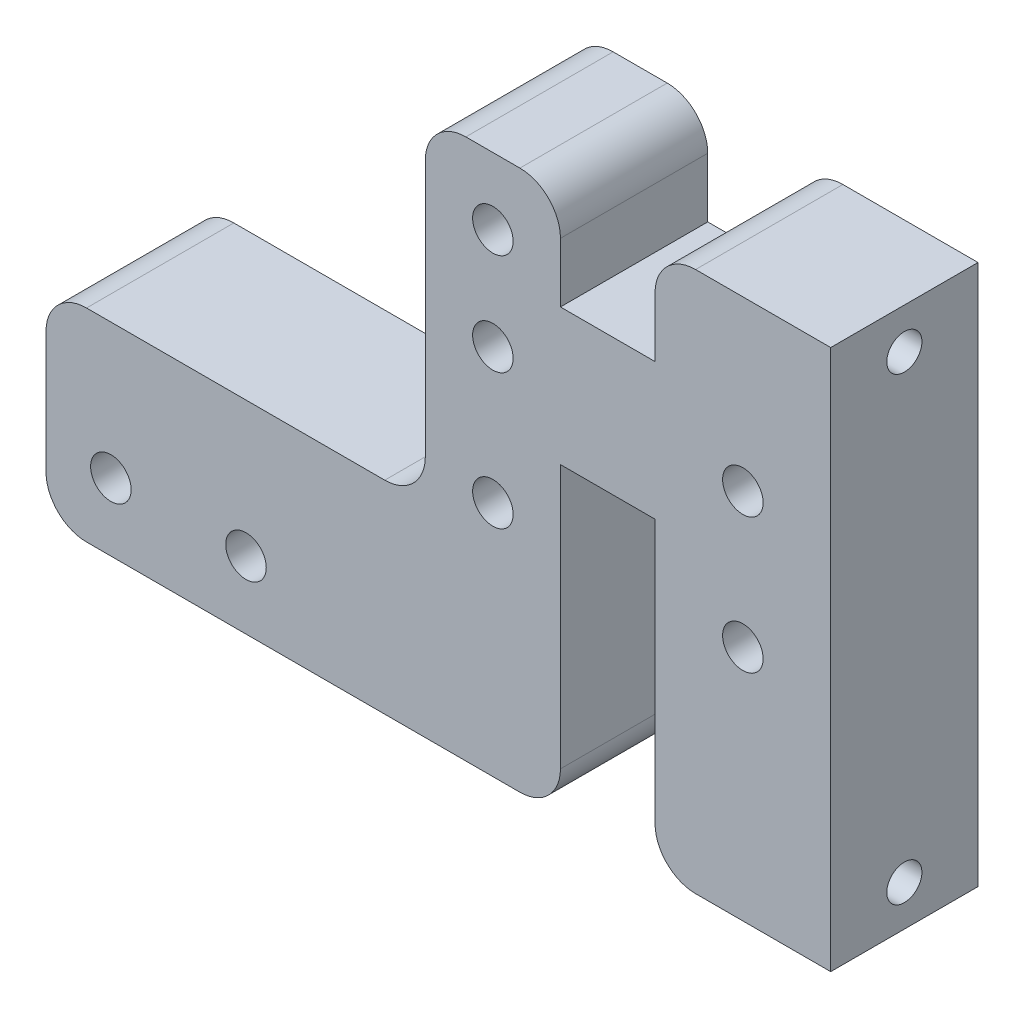
SolidWorks part; units mm, degrees
material "ナイロン"
ref_plane "正面" through (0, 0, 0) normal (0, 0, 1) x (1, 0, 0)
ref_plane "平面" through (0, 0, 0) normal (0, 1, 0) x (1, 0, 0)
ref_plane "右側面" through (0, 0, 0) normal (1, 0, 0) x (0, 0, -1)
sketch "ｽｹｯﾁ1" plane through (0, 0, 0) normal (0, 0, 1) x (1, 0, 0)
  line L0 (9.035, 20) -> (9.035, 12.6)
  line L1 (-29.035, -20) -> (29.035, -20)
  line L2 (-29.035, -20) -> (-29.035, 20)
  line L3 (-29.035, 20) -> (29.035, 20)
  line L4 (29.035, -20) -> (29.035, 20)
  line L5 (-29.035, -20) -> (29.035, 20) construction
  line L6 (-29.035, 20) -> (29.035, -20) construction
  line L7 (9.035, 12.6) -> (16.035, 12.6)
  line L8 (16.035, 12.6) -> (16.035, 20)
  line L9 (9.035, -20) -> (9.035, 2.5)
  line L10 (9.035, 2.5) -> (16.035, 2.5)
  line L11 (16.035, 2.5) -> (16.035, -20)
  line L12 (22.535, 20) -> (22.535, -20) construction
  line L13 (12.535, 12.6) -> (12.535, 2.5) construction
  line L14 (12.535, 7.55) -> (29.035, 7.55) construction
  line L15 (22.535, -2.45) -> (4.035, -2.45) construction
  line L16 (4.035, -2.45) -> (4.035, 7.55) construction
  line L17 (4.035, 7.55) -> (4.035, 15.05) construction
  circle A0 centre (22.535, 7.55) radius 1.5
  circle A1 centre (22.535, -2.45) radius 1.5
  circle A2 centre (4.035, -2.45) radius 1.5
  circle A3 centre (4.035, 7.55) radius 1.5
  circle A4 centre (4.035, 15.05) radius 1.5
  point P0 (0, 0)
  dimension "D7" = 10
  dimension "D8" = 3
  dimension "D9" = 3
  dimension "D10" = 10
  dimension "D11" = 5
  dimension "D1" = 40
  dimension "D2" = 13
  dimension "D3" = 7
  dimension "D4" = 7.4
  dimension "D5" = 58.07
  dimension "D6" = 22.5
  dimension "D12" = 7.5
extrude "ﾎﾞｽ - 押し出し1" add sketch "ｽｹｯﾁ1" along normal blind 10.9 contours L8 L7 L0 L3 L2 L1 L4 region at (-1.4569, 0.171, 0)
sketch "ｽｹｯﾁ2" plane through (29.035, 0, 0) normal (1, 0, 0) x (0, 0, -1)
  line L0 (-5.45, 20) -> (-5.45, -20) construction
  line L1 (-10.9, 20) -> (0, 20) construction
  line L2 (-10.9, -20) -> (0, -20) construction
  line L3 (0, 0) -> (-10.9, 0) construction
  line L4 (-10.9, -20) -> (-10.9, 20) construction
  circle A0 centre (-5.45, 17) radius 1.3
  circle A1 centre (-5.45, -17) radius 1.3
  dimension "D1" = 34
  dimension "D2" = 2.6
extrude "ｶｯﾄ - 押し出し1" cut sketch "ｽｹｯﾁ2" against normal up to surface (13 mm away) up to face at (16.035, 16.3, 5.45)
sketch "ｽｹｯﾁ5" plane through (0, 0, 10.9) normal (0, 0, 1) x (1, 0, 0)
  line L0 (29.035, -20) -> (29.035, 20) construction
  line L1 (-29.035, 20) -> (9.035, 20) construction
  line L2 (-8.935, 24) -> (-29.035, 24) construction
  circle A0 centre (-29.035, 24) radius 5.1
  circle A1 centre (-8.935, 24) radius 5.1
  dimension "D1" = 58.07
  dimension "D2" = 20.1
  dimension "D3" = 10.2
  dimension "D4" = 4
extrude "ｶｯﾄ - 押し出し3" cut sketch "ｽｹｯﾁ5" against normal through all
sketch "ｽｹｯﾁ3" plane through (0, 0, 10.9) normal (0, 0, 1) x (1, 0, 0)
  line L1 (-5.7711, 20) -> (9.035, 20) construction
  line L2 (-37.035, 24) -> (-37.035, -20)
  line L3 (-34.6919, 29.6569) -> (-23.3781, 18.3431)
  line L4 (-25.4288, 20.3938) -> (-25.4288, 20)
  line L5 (-13.435, 21.8206) -> (-13.435, 20)
  line L6 (-8.935, 29) -> (-8.935, 50029) construction
  line L7 (-4.435, 21.8206) -> (-4.435, 20)
  line L9 (-8.935, 24) -> (-29.035, 24) construction
  line L10 (-25.8711, 20) -> (-12.0989, 20) construction
  line L11 (-37.035, -20) -> (-29.035, -20)
  line L12 (-29.035, -20) -> (9.035, -20) construction
  line L13 (-29.035, -20) -> (-29.035, 18.9) construction
  circle A0 centre (-29.035, 24) radius 8
  circle A1 centre (-29.035, 24) radius 5.1
  circle A2 centre (-8.935, 24) radius 8
  circle A3 centre (-8.935, 24) radius 5.1
  circle A4 centre (-8.935, 24) radius 5 construction
  arc A14 (-12.0989, 20) -> (-5.7711, 20) centre (-8.935, 24) ccw construction
  dimension "D2" = 16
  dimension "D3" = 10.2
  dimension "D5" = 20.1
  dimension "D6" = 10
  dimension "D4" = 45
  dimension "D7" = 9
extrude "ﾎﾞｽ - 押し出し2" [suppressed] add sketch "ｽｹｯﾁ3" against normal up to surface (10.9 mm away)
sketch "ｽｹｯﾁ4" [suppressed] plane through (0, 0, 10.9) normal (0, 0, 1) x (1, 0, 0)
  line L0 (-19.235, 21) -> (-19.235, 50021) construction
  line L1 (-25.035, 20) -> (-13.435, 20) construction
  line L2 (-37.035, -20) -> (9.035, -20) construction
  line L3 (-28.735, -4.2) -> (-9.735, -4.2)
  line L4 (-28.735, -4.2) -> (-28.735, 25.8)
  line L5 (-28.735, 25.8) -> (-9.735, 25.8)
  line L6 (-9.735, -4.2) -> (-9.735, 25.8)
  line L7 (-28.735, -4.2) -> (-9.735, 25.8) construction
  line L8 (-28.735, 25.8) -> (-9.735, -4.2) construction
  line L9 (9.035, 20) -> (9.035, 12.6) construction
  line L10 (-4.435, 20) -> (9.035, 20) construction
  line L11 (-37.035, -15) -> (9.035, -15) construction
  line L12 (-37.035, 24) -> (-37.035, -20) construction
  line L13 (9.035, -20) -> (9.035, 10) construction
  line L14 (-37.035, -20) -> (9.035, -20) construction
  circle A2 centre (4.035, 10) radius 1.5
  circle A3 centre (-14.235, -15) radius 2
  circle A4 centre (-24.235, -15) radius 2
  point P4 (-19.235, 20)
  point P5 (-19.235, 10.8)
  dimension "D3" = 4
  dimension "D7" = 5
  dimension "D8" = 10
  dimension "D9" = 3
  dimension "D10" = 10
  dimension "D1" = 15.8
  dimension "D2" = 19
  dimension "D6" = 30
  dimension "D11" = 5
extrude "ｶｯﾄ - 押し出し2" [suppressed] cut sketch "ｽｹｯﾁ4" against normal through all
fillet "ﾌｨﾚｯﾄ1" [suppressed] radius 3
sketch "ｽｹｯﾁ6" plane through (0, 0, 10.9) normal (0, 0, 1) x (1, 0, 0)
  line L0 (-29.035, -15) -> (-24.235, -15) construction
  line L1 (-29.035, -20) -> (-29.035, 18.9) construction
  line L2 (-24.235, -15) -> (-14.235, -15) construction
  line L3 (-29.035, -20) -> (9.035, -20) construction
  circle A0 centre (-24.235, -15) radius 1.5
  circle A1 centre (-14.235, -15) radius 1.5
  dimension "D1" = 4.8
  dimension "D2" = 10
  dimension "D3" = 3
  dimension "D4" = 5
extrude "ｶｯﾄ - 押し出し4" cut sketch "ｽｹｯﾁ6" against normal through all
sketch "ｽｹｯﾁ7" plane through (0, 0, 10.9) normal (0, 0, 1) x (1, 0, 0)
  line L0 (-29.035, -20) -> (-29.035, 18.9) construction
  line L1 (-29.035, -5) -> (-0.965, -5)
  line L2 (-29.035, -5) -> (-29.035, 20)
  line L3 (-29.035, 20) -> (-0.965, 20)
  line L4 (-0.965, -5) -> (-0.965, 20)
  line L5 (-5.7711, 20) -> (9.035, 20) construction
  line L6 (9.035, 20) -> (9.035, 12.6) construction
  circle A0 centre (-14.235, -15) radius 1.5 construction
  dimension "D1" = 10
  dimension "D2" = 10
extrude "ｶｯﾄ - 押し出し5" cut sketch "ｽｹｯﾁ7" against normal through all
fillet "ﾌｨﾚｯﾄ2" radius 3 8 edges at (16.035, -20, 5.45) (9.035, -20, 5.45) (-29.035, -20, 5.45) (-29.035, -5, 5.45) (-0.965, -5, 5.45) (-0.965, 20, 5.45) (16.035, 20, 5.45) (9.035, 20, 5.45)
